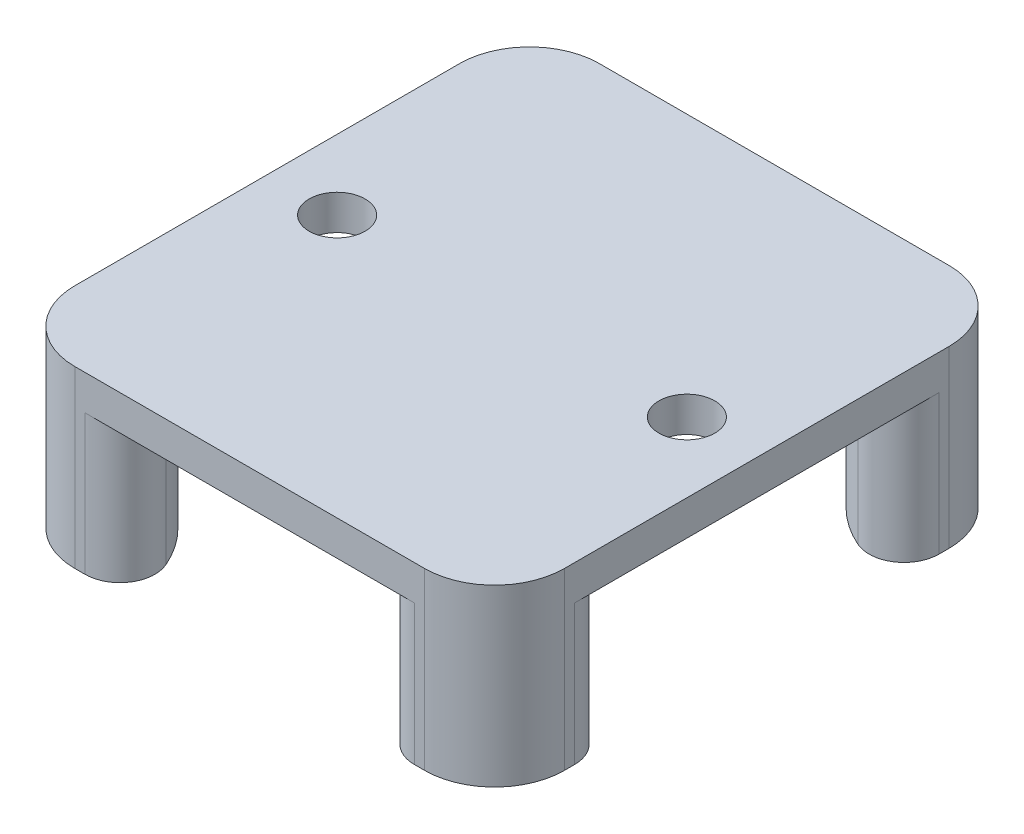
SolidWorks part; units mm, degrees
ref_plane "Płaszczyzna przednia" through (0, 0, 0) normal (0, 0, 1) x (1, 0, 0)
ref_plane "Płaszczyzna górna" through (0, 0, 0) normal (0, 1, 0) x (1, 0, 0)
ref_plane "Płaszczyzna prawa" through (0, 0, 0) normal (1, 0, 0) x (0, 0, -1)
sketch "Szkic1" plane through (0, 0, 0) normal (0, 1, 0) x (1, 0, 0)
  line L0 (-10, 0) -> (10, 0) construction
  line L2 (-14, -15) -> (14, -15)
  line L3 (-14, -15) -> (-14, 15)
  line L4 (-14, 15) -> (14, 15)
  line L5 (14, -15) -> (14, 15)
  line L6 (-14, -15) -> (14, 15) construction
  line L7 (-14, 15) -> (14, -15) construction
  circle A0 centre (10, 0) radius 1.6
  circle A1 centre (-10, 0) radius 1.6
  point P4 (0, 0)
  point P7 (0, 0)
  dimension "D1" = 3.2
  dimension "D2" = 3.2
  dimension "D3" = 28
  dimension "D4" = 30
  dimension "D5" = 20
extrude "Dodanie-wyciągnięcie1" add sketch "Szkic1" along normal blind 2
sketch "Szkic2" plane through (0, 0, 0) normal (0, -1, 0) x (1, 0, 0)
  line L0 (-14, 15) -> (14, 15) construction
  line L1 (-14, -15) -> (-14, 15) construction
  line L2 (-14, 8) -> (-14, 15)
  line L3 (-14, 15) -> (-7, 15)
  line L4 (0, -55) -> (0, 55) construction
  line L5 (14, 8) -> (14, 15)
  line L6 (14, 15) -> (7, 15)
  line L7 (55, 0) -> (-55, 0) construction
  line L8 (14, -15) -> (7, -15)
  line L9 (14, -8) -> (14, -15)
  line L10 (-14, -8) -> (-14, -15)
  line L11 (-14, -15) -> (-7, -15)
  arc A0 (-7, 15) -> (-14, 8) centre (-14, 15) cw
  arc A1 (7, 15) -> (14, 8) centre (14, 15) ccw
  arc A2 (7, -15) -> (14, -8) centre (14, -15) cw
  arc A3 (-7, -15) -> (-14, -8) centre (-14, -15) ccw
  dimension "D1" = 7
extrude "Dodanie-wyciągnięcie2" add sketch "Szkic2" along normal blind 8
fillet "Zaokrąglenie1" radius 4 4 edges at (-14, -3, 15) (14, -3, 15) (14, -3, -15) (-14, -3, -15)
fillet "Zaokrąglenie2" radius 2 8 edges at (-14, -4, 8) (-7, -4, 15) (14, -4, 8) (7, -4, 15) (-14, -4, -8) (-7, -4, -15) (14, -4, -8) (7, -4, -15)
